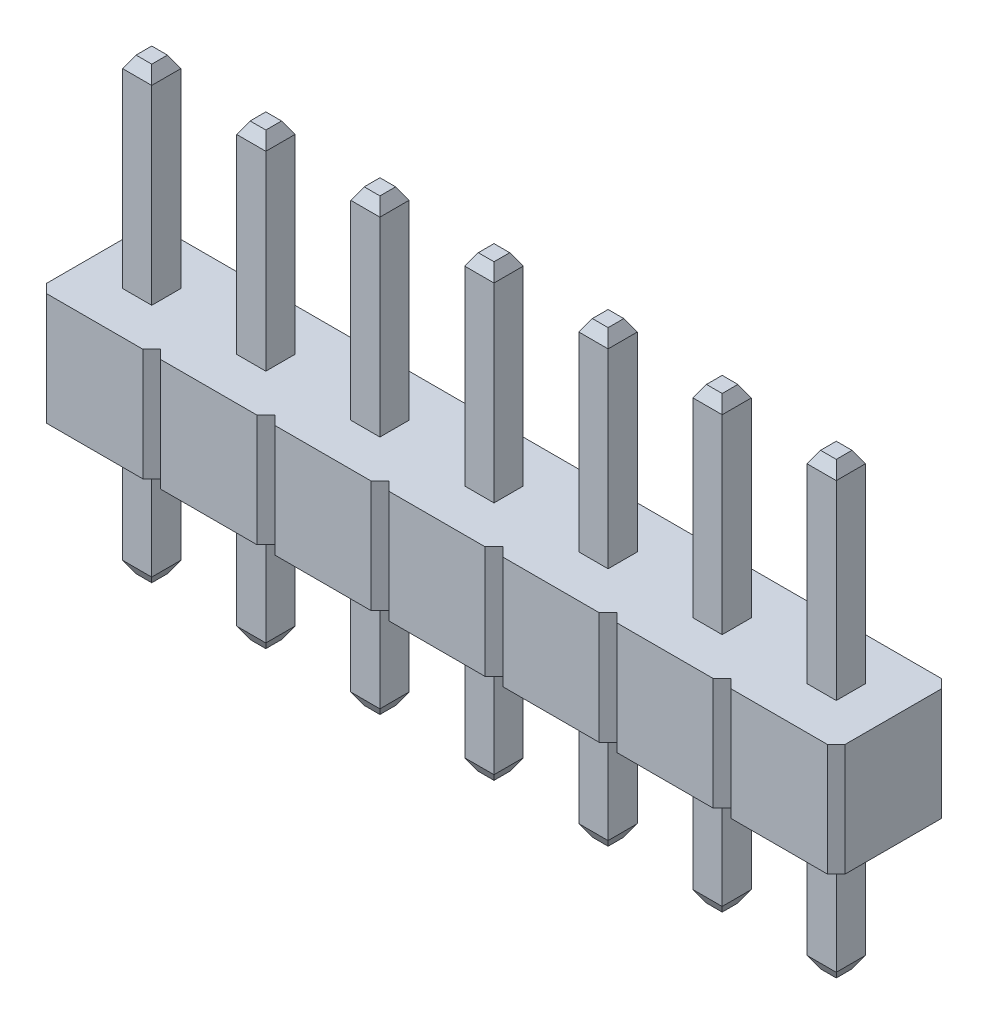
SolidWorks part; units mm, degrees
ref_plane "Front Plane" through (0, 0, 0) normal (0, 0, 1) x (1, 0, 0)
ref_plane "Top Plane" through (0, 0, 0) normal (0, 1, 0) x (1, 0, 0)
ref_plane "Right Plane" through (0, 0, 0) normal (1, 0, 0) x (0, 0, -1)
sketch "Sketch1" plane through (0, 0, 0) normal (0, 1, 0) x (1, 0, 0)
  line L0 (-7.42, 1.27) -> (-7.62, 1.07)
  line L1 (-7.62, 1.27) -> (7.62, 1.27) construction
  line L2 (-7.62, 1.27) -> (-7.62, -1.27) construction
  line L3 (-7.62, -1.27) -> (7.62, -1.27) construction
  line L4 (7.62, 1.27) -> (7.62, -1.27) construction
  line L5 (-7.62, 1.27) -> (7.62, -1.27) construction
  line L6 (-7.62, -1.27) -> (7.62, 1.27) construction
  line L7 (-5.28, -1.27) -> (-7.42, -1.27)
  line L8 (-5.08, -1.07) -> (-5.08, 1.07)
  line L9 (-5.28, 1.27) -> (-7.42, 1.27)
  line L10 (-7.62, -1.07) -> (-7.62, 1.07)
  line L11 (-5.08, -1.27) -> (-7.62, 1.27) construction
  line L12 (-5.08, 1.27) -> (-7.62, -1.27) construction
  line L13 (-5.08, 1.07) -> (-5.28, 1.27)
  line L14 (-7.42, -1.27) -> (-7.62, -1.07)
  line L15 (-5.08, -1.07) -> (-5.28, -1.27)
  point P0 (0, 0)
  point P6 (-6.35, 0)
  dimension "D1" = 15.24
  dimension "D2" = 2.54
extrude "Boss-Extrude1" add sketch "Sketch1" along normal blind 2.5
ref_plane "Plane1" through (0, -3, 0) normal (0, 1, 0) x (1, 0, 0)
sketch "Sketch3" plane through (0, -3, 0) normal (0, 1, 0) x (1, 0, 0)
  line L0 (-7.52, -1.17) -> (-5.18, 1.17) construction
  line L1 (-7.62, -1.07) -> (-7.42, -1.27) construction
  line L2 (-5.08, 1.07) -> (-5.28, 1.27) construction
  line L4 (-6.675, 0.325) -> (-6.025, 0.325)
  line L5 (-6.675, 0.325) -> (-6.675, -0.325)
  line L6 (-6.675, -0.325) -> (-6.025, -0.325)
  line L7 (-6.025, 0.325) -> (-6.025, -0.325)
  line L8 (-6.675, 0.325) -> (-6.025, -0.325) construction
  line L9 (-6.675, -0.325) -> (-6.025, 0.325) construction
  circle A0 centre (-6.35, 0) radius 0.325 construction
  dimension "D1" = 0.65
extrude "Boss-Extrude2" add sketch "Sketch3" along normal blind 10
chamfer "Chamfer2" distance 0.15 angle 60 4 edges at (-6.35, -3, -0.325) (-6.675, -3, 0) (-6.35, -3, 0.325) (-6.025, -3, 0)
ref_plane "Plane2" through (0, 1.25, 0) normal (0, -1, 0) x (-1, 0, 0)
chamfer "Chamfer3" distance 0.15 angle 60 4 edges at (-6.35, 7, 0.325) (-6.675, 7, 0) (-6.35, 7, -0.325) (-6.025, 7, 0)
pattern_linear "LPattern2" count 7 spacing 2.54 along (1, 0, 0) of "Boss-Extrude1", "Boss-Extrude2", "Chamfer2", "Chamfer3"
